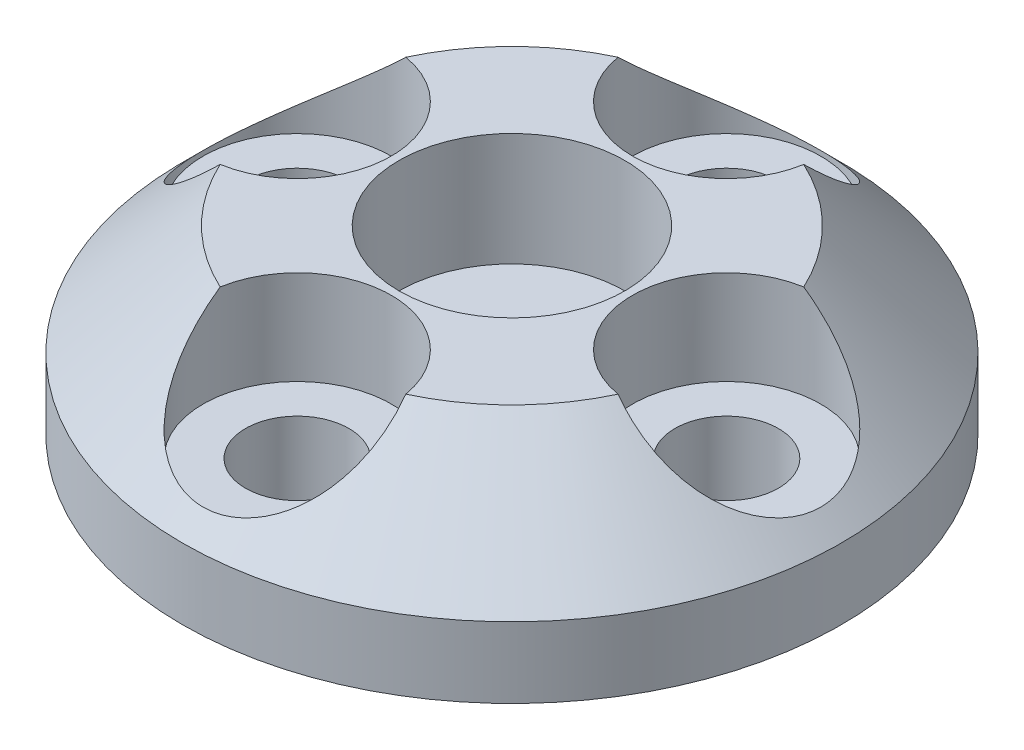
SolidWorks part; units mm, degrees
ref_plane "Front Plane" through (0, 0, 0) normal (0, 0, 1) x (1, 0, 0)
ref_plane "Top Plane" through (0, 0, 0) normal (0, 1, 0) x (1, 0, 0)
ref_plane "Right Plane" through (0, 0, 0) normal (1, 0, 0) x (0, 0, -1)
sketch "Sketch1" plane through (0, 0, 0) normal (0, 1, 0) x (1, 0, 0)
  circle A0 centre (0, 0) radius 8.75
extrude "Boss-Extrude1" add sketch "Sketch1" along normal blind 4.8
sketch "Sketch2" plane through (0, 4.8, 0) normal (0, 1, 0) x (1, 0, 0)
  circle A0 centre (0, 0) radius 3
extrude "Cut-Extrude1" cut sketch "Sketch2" against normal blind 3
sketch "Sketch3" plane through (0, 4.8, 0) normal (0, 1, 0) x (1, 0, 0)
  circle A0 centre (0, 0) radius 5.7 construction
  circle A1 centre (-5.7, 0) radius 2.5
  circle A2 centre (0, 5.7) radius 2.5
  circle A3 centre (5.7, 0) radius 2.5
  circle A4 centre (0, -5.7) radius 2.5
extrude "Cut-Extrude2" cut sketch "Sketch3" against normal blind 2.5
sketch "Sketch4" plane through (0, 2.3, 0) normal (0, 1, 0) x (1, 0, 0)
  circle A0 centre (-5.7, 0) radius 1.375
  circle A1 centre (0, 5.7) radius 1.375
  circle A2 centre (5.7, 0) radius 1.375
  circle A3 centre (0, -5.7) radius 1.375
  dimension "D1" = 2.75
extrude "Cut-Extrude3" cut sketch "Sketch4" against normal blind 2.5
chamfer "Chamfer1" distance 2.921 angle 45 1 edges at (0, 4.8, 8.75)
